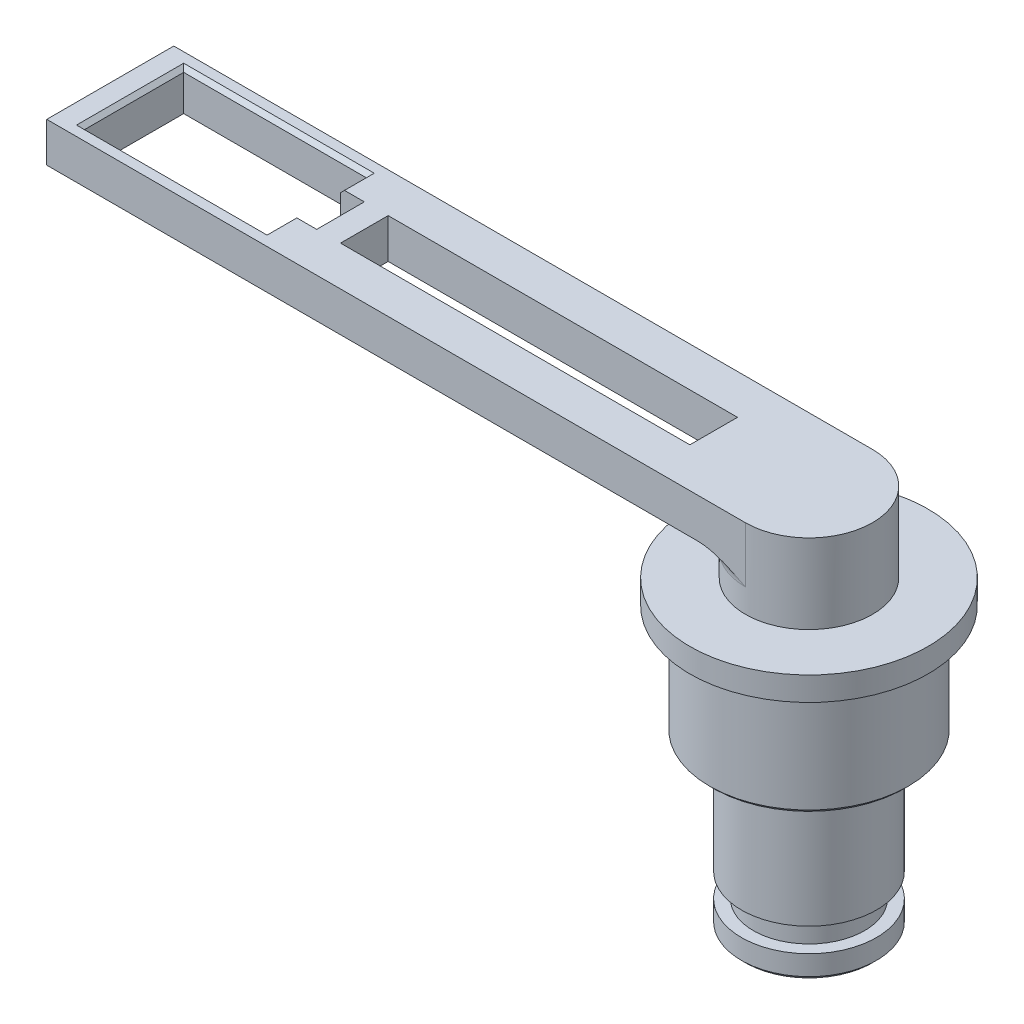
SolidWorks part; units mm, degrees
ref_plane "Plan de face" through (0, 0, 0) normal (0, 0, 1) x (1, 0, 0)
ref_plane "Plan de dessus" through (0, 0, 0) normal (0, 1, 0) x (1, 0, 0)
ref_plane "Plan de droite" through (0, 0, 0) normal (1, 0, 0) x (0, 0, -1)
sketch "Sketch1" plane through (0, 0, 0) normal (0, 1, 0) x (1, 0, 0)
  line L1 (0, 8) -> (-88, 8)
  line L2 (0, 8) -> (0, -8)
  line L3 (0, -8) -> (-88, -8)
  line L4 (-88, 8) -> (-88, -8)
  line L5 (-85, 6.25) -> (-62, 6.25)
  line L6 (-85, 6.25) -> (-85, -6.25)
  line L7 (-85, -6.25) -> (-62, -6.25)
  line L8 (-62, 6.25) -> (-62, -6.25)
  line L9 (-85, 6.25) -> (-62, -6.25) construction
  line L10 (-85, -6.25) -> (-62, 6.25) construction
  point P4 (0, 0)
  point P6 (-73.5, 0)
  dimension "D1" = 88
  dimension "D2" = 16
  dimension "D3" = 3
  dimension "D4" = 23
  dimension "D5" = 12.5
extrude "Boss-Extrude1" add sketch "Sketch1" along normal blind 5
sketch "Sketch2" plane through (0, 0, 0) normal (0, -1, 0) x (1, 0, 0)
  circle A0 centre (0, 0) radius 8
extrude "Boss-Extrude2" add sketch "Sketch2" along normal blind 5 and the other way up to surface (5 mm away) other way up to face at (-44, 5, 0)
fillet "Fillet1" radius 2 1 edges at (-8, 0, 0)
sketch "Sketch11" plane through (0, 0, 0) normal (0, 0, 1) x (1, 0, 0)
  line L0 (0, -5) -> (0, -43) construction
  line L1 (-8, -5) -> (8, -5) construction
  line L2 (0, -5) -> (15, -5)
  line L3 (15, -5) -> (15, -8)
  line L4 (15, -8) -> (12.5, -8)
  line L5 (12.5, -8) -> (12.5, -22)
  line L6 (12.5, -22) -> (8.5, -22)
  line L7 (8.5, -22) -> (8.5, -37)
  line L8 (8.5, -37) -> (7, -37)
  line L9 (7, -37) -> (7, -40)
  line L10 (7, -40) -> (8.5, -40)
  line L11 (8.5, -40) -> (8.5, -43)
  line L12 (8.5, -43) -> (0, -43)
  line L14 (0, -5) -> (0, -43)
  dimension "D1" = 30
  dimension "D2" = 25
  dimension "D3" = 3
  dimension "D4" = 14
  dimension "D5" = 17
  dimension "D6" = 21
  dimension "D7" = 3
  dimension "D8" = 3
  dimension "D9" = 14
  dimension "D10" = 17
revolve "Revolve1" add sketch "Sketch11" angle 360 about L0
chamfer "Chamfer1" distance 0.5 angle 45 2 edges at (-8.5, -43, 0) (-12.5, -22, 0)
sketch "Sketch5" plane through (0, -43, 0) normal (0, -1, 0) x (1, 0, 0)
  line L0 (-1.45, 2.569) -> (-1.45, -2.569)
  line L1 (1.45, 2.569) -> (1.45, -2.569)
  arc A0 (-1.45, -2.569) -> (1.45, -2.569) centre (0, 0) ccw
  arc A1 (1.45, 2.569) -> (-1.45, 2.569) centre (0, 0) ccw
  dimension "D1" = 5.9
  dimension "D2" = 1.45
  dimension "D3" = 1.45
extrude "Cut-Extrude1" cut sketch "Sketch5" against normal blind 8
sketch "Sketch6" plane through (0, 5, 0) normal (0, 1, 0) x (1, 0, 0)
  line L0 (-62, -6.25) -> (-62, 6.25) construction
  line L1 (-62, -3) -> (-59, -3)
  line L2 (-62, -3) -> (-62, 3)
  line L3 (-62, 3) -> (-59, 3)
  line L4 (-59, -3) -> (-59, 3)
  line L7 (-56, 3) -> (-12, 3)
  line L8 (-56, 3) -> (-56, -3)
  line L9 (-56, -3) -> (-12, -3)
  line L10 (-12, 3) -> (-12, -3)
  point P6 (-62, 0)
  point P7 (-62, 0)
  dimension "D1" = 6
  dimension "D2" = 3
  dimension "D3" = 50
  dimension "D4" = 3
extrude "Cut-Extrude2" cut sketch "Sketch6" against normal up to surface (5 mm away) up to face at (-48, 0, 0)
chamfer "Chamfer2" distance 0.5 angle 45 5 edges at (-62, 5, -4.625) (-62, 5, 4.625) (-73.5, 5, 6.25) (-85, 5, 0) (-73.5, 5, -6.25)
shell "Shell1" [suppressed] thickness 2
